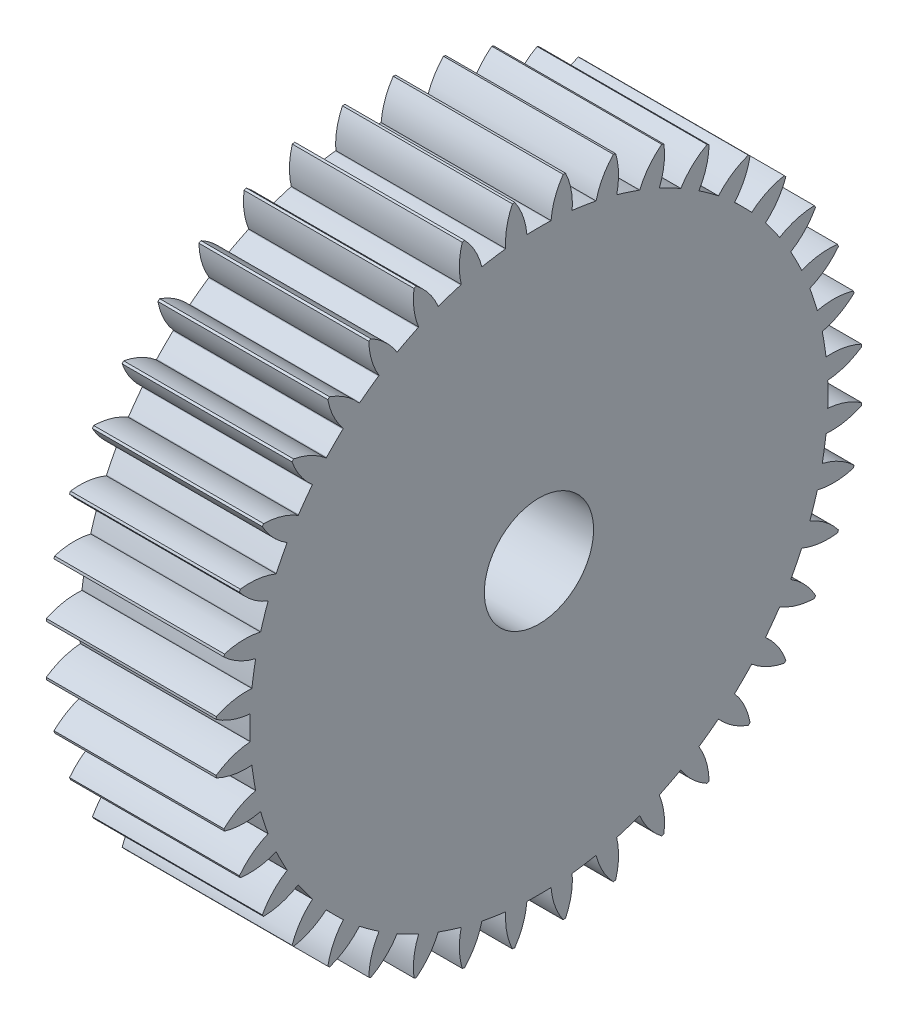
SolidWorks part; units mm, degrees
ref_plane "Front Plane" through (0, 0, 0) normal (0, 0, 1) x (1, 0, 0)
ref_plane "Top Plane" through (0, 0, 0) normal (0, 1, 0) x (1, 0, 0)
ref_plane "Right Plane" through (0, 0, 0) normal (1, 0, 0) x (0, 0, -1)
sketch "Sketch1" plane through (0, 0, 0) normal (1, 0, 0) x (0, 0, -1)
  circle A0 centre (0, 0) radius 133.35
  dimension "D1" = 266.7
extrude "Boss-Extrude1" add sketch "Sketch1" along normal mid plane 70
sketch "Sketch6" plane through (35, 0, 0) normal (1, 0, 0) x (0, 0, -1)
  circle A0 centre (0, 0) radius 22.5
  dimension "D1" = 45
extrude "Cut-Extrude4" cut sketch "Sketch6" against normal through all
sketch "Sketch7" plane through (35, 0, 0) normal (1, 0, 0) x (0, 0, -1)
  line L0 (0, 0) -> (0, 238.2) construction
  line L1 (0, 119.1) -> (-4.985, 118.9606)
  line L2 (0, 119.1) -> (4.985, 118.9606)
  line L3 (-9.975, 132.9764) -> (0, 140.9758)
  line L4 (9.975, 132.9764) -> (0, 140.9758)
  circle A0 centre (0, 0) radius 119.065 construction
  circle A1 centre (0, 0) radius 127 construction
  arc A2 (-4.985, 118.9606) -> (-9.975, 132.9764) centre (-33.8353, 116.5853) ccw
  circle A3 centre (0, 0) radius 133.35 construction
  arc A4 (4.985, 118.9606) -> (9.975, 132.9764) centre (33.8353, 116.5853) cw
  point P12 (0, 134.345)
  point P16 (0, 106.365)
  point P17 (0, 106.365)
  point P18 (0, 106.365)
  point P19 (0, 106.3837)
  point P20 (0, 119.6702)
  point P21 (0, 140.9758)
  point P22 (0, 0)
  point P23 (0, 119.3191)
  point P24 (0, 119.2319)
  point P25 (0, 119.1)
  dimension "D1" = 254
  dimension "D2" = 238.13
  dimension "D3" = 4.99
  dimension "D4" = 19.95
extrude "Cut-Extrude5" cut sketch "Sketch7" against normal through all
fillet "Fillet2" radius 170 1 edges at (0, 119.1, 0)
pattern_circular "CirPattern2" count 40 over 360 about axis through (35, 0, 0) along (1, 0, 0) of "Fillet2", "Cut-Extrude5"
